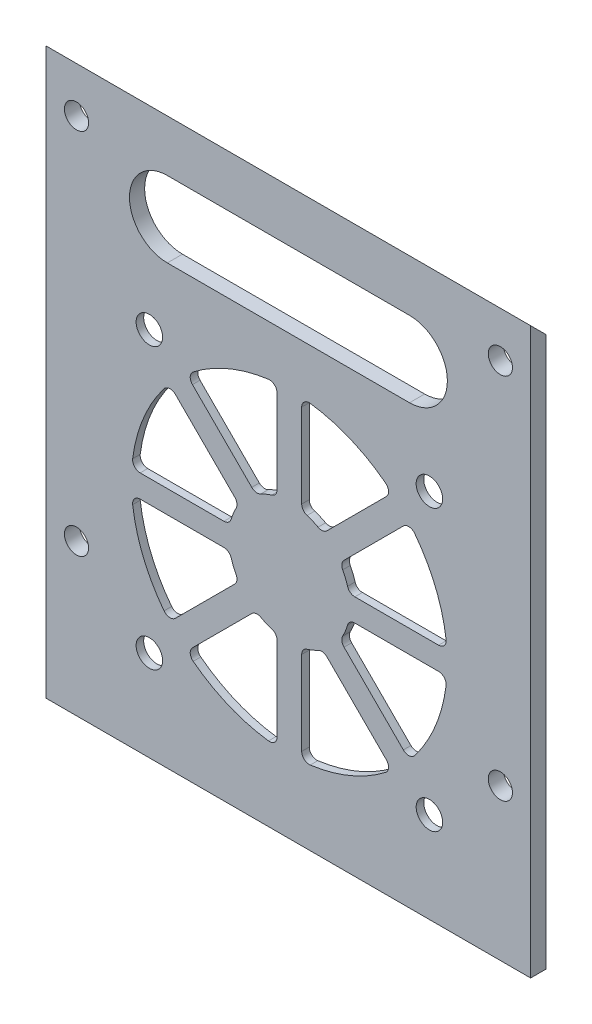
SolidWorks part; units mm, degrees
ref_plane "Płaszczyzna przednia" through (0, 0, 0) normal (0, 0, 1) x (1, 0, 0)
ref_plane "Płaszczyzna górna" through (0, 0, 0) normal (0, 1, 0) x (1, 0, 0)
ref_plane "Płaszczyzna prawa" through (0, 0, 0) normal (1, 0, 0) x (0, 0, -1)
sketch "Szkic1" plane through (0, 0, 0) normal (0, 0, 1) x (1, 0, 0)
  line L1 (-64, 0) -> (0, 0)
  line L2 (-64, 0) -> (-64, 72.64)
  line L3 (-64, 72.64) -> (0, 72.64)
  line L4 (0, 0) -> (0, 72.64)
  line L5 (0, 72.64) -> (-64, 72.64)
  line L6 (0, 72.64) -> (0, 74.64)
  line L7 (0, 74.64) -> (-64, 74.64)
  line L8 (-64, 72.64) -> (-64, 74.64)
extrude "Dodanie-wyciągnięcie1" add sketch "Szkic1" along normal blind 2 contours L8 L3 L6 L7 | L1 L4 L3 L2 region at (-32, 36.32, 0) region at (-32, 73.64, 0)
chamfer "Sfazowanie1" distance 2 angle 45 1 edges at (-32, 74.64, 0)
sketch "Szkic2" plane through (0, 0, 2) normal (0, 0, 1) x (1, 0, 0)
  line L0 (-56, 16) -> (-64, 16) construction
  line L2 (0, 72.64) -> (-64, 72.64) construction
  line L3 (0, 0) -> (0, 74.64) construction
  line L4 (-64, 0) -> (-64, 74.64) construction
  line L5 (-8, 16) -> (0, 16) construction
  line L6 (-56, 0) -> (-56, 16) construction
  line L7 (-64, 0) -> (0, 0) construction
  line L8 (-8, 0) -> (-8, 16) construction
  line L9 (-8, 16) -> (-8, 24) construction
  line L10 (-56, 16) -> (-56, 24) construction
  line L11 (-56, 72.64) -> (-56, 64.64) construction
  line L12 (-8, 72.64) -> (-8, 64.64) construction
  line L13 (-56, 64.64) -> (-64, 64.64) construction
  line L14 (-8, 64.64) -> (0, 64.64) construction
  line L15 (-56, 64.64) -> (-64, 72.64) construction
  line L16 (-8, 72.64) -> (0, 64.64) construction
  line L17 (-56, 24) -> (-64, 16) construction
  line L18 (-8, 24) -> (0, 16) construction
  circle A0 centre (-60, 20) radius 1.6
  circle A1 centre (-4, 20) radius 1.6
  circle A2 centre (-4, 68.64) radius 1.6
  circle A3 centre (-60, 68.64) radius 1.6
extrude "Wytnij-wyciągnięcie1" cut sketch "Szkic2" against normal blind 2
sketch "Szkic3" plane through (0, 0, 0) normal (0, 0, -1) x (-1, 0, 0)
  line L0 (31.8747, 30.5) -> (52.7469, 30.5)
  line L1 (31.8747, 30.5) -> (31.8747, 51.3722)
  line L2 (31.8747, 30.5) -> (11.0024, 30.5)
  line L3 (31.8747, 30.5) -> (31.8747, 9.6278)
  line L4 (31.8747, 30.5) -> (46.6336, 45.2589)
  line L5 (31.8747, 30.5) -> (17.1158, 45.2589)
  line L6 (31.8747, 30.5) -> (17.1158, 15.7411)
  line L7 (31.8747, 30.5) -> (46.6336, 15.7411)
  line L8 (17.1158, 45.2589) -> (46.6336, 15.7411) construction
  line L9 (18.2403, 46.3834) -> (47.7581, 16.8656)
  line L10 (15.9912, 44.1344) -> (45.509, 14.6166)
  line L11 (31.8747, 51.3722) -> (31.8747, 9.6278) construction
  line L12 (33.5024, 51.3722) -> (33.5024, 9.6278)
  line L13 (30.2469, 51.3722) -> (30.2469, 9.6278)
  line L14 (46.6336, 45.2589) -> (17.1158, 15.7411) construction
  line L15 (47.7581, 44.1344) -> (18.2403, 14.6166)
  line L16 (45.509, 46.3834) -> (15.9912, 16.8656)
  line L17 (52.7469, 30.5) -> (11.0024, 30.5) construction
  line L18 (52.7469, 29) -> (11.0024, 29)
  line L19 (52.7469, 32) -> (11.0024, 32)
  circle A0 centre (31.8747, 30.5) radius 20.8722
  circle A1 centre (31.8747, 30.5) radius 8
  arc A2 (18.2403, 46.3834) -> (15.9912, 44.1344) centre (17.1158, 45.2589) ccw
  arc A3 (45.509, 14.6166) -> (47.7581, 16.8656) centre (46.6336, 15.7411) ccw
  arc A4 (33.5024, 51.3722) -> (30.2469, 51.3722) centre (31.8747, 51.3722) ccw
  arc A5 (30.2469, 9.6278) -> (33.5024, 9.6278) centre (31.8747, 9.6278) ccw
  arc A6 (47.7581, 44.1344) -> (45.509, 46.3834) centre (46.6336, 45.2589) ccw
  arc A7 (15.9912, 16.8656) -> (18.2403, 14.6166) centre (17.1158, 15.7411) ccw
  arc A8 (52.7469, 29) -> (52.7469, 32) centre (52.7469, 30.5) ccw
  arc A9 (11.0024, 32) -> (11.0024, 29) centre (11.0024, 30.5) ccw
  point P4 (31.8747, 30.5)
  point P17 (31.8747, 30.5)
  point P22 (31.8747, 30.5)
  point P27 (31.8747, 30.5)
extrude "Wytnij-wyciągnięcie2" cut sketch "Szkic3" against normal blind 10 contours A1 L10 A0 L19 | A1 L18 A0 L16 | A1 L13 A0 L9 | A1 L16 A0 L12 | A1 L19 A0 L15 | A1 L9 A0 L18 | A1 L12 A0 L10 | A1 L15 A0 L13 region at (-46.2358, 36.4001, 0) region at (-46.2358, 24.5999, 0) region at (-37.8435, 44.8616, 0) region at (-37.8435, 16.1384, 0) region at (-25.9058, 44.8616, 0) region at (-17.5136, 36.4001, 0) region at (-17.5136, 24.5999, 0) region at (-25.9058, 16.1384, 0)
fillet "Zaokrąglenie1" radius 1 32 edges at (-39.7328, 32, 1) (-52.6929, 32, 1) (-38.5432, 34.9194, 1) (-47.7152, 44.0915, 1) (-33.5024, 51.3087, 1) (-45.4661, 46.3405, 1) (-36.2941, 37.1685, 1) (-33.5024, 38.3326, 1) (-18.2832, 46.3405, 1) (-30.2469, 51.3087, 1) (-30.2469, 38.3326, 1) (-27.4553, 37.1685, 1) (-16.0341, 44.0915, 1) (-25.2062, 34.9194, 1) (-24.0166, 32, 1) (-11.0564, 32, 1) (-16.0341, 16.9085, 1) (-25.2062, 26.0806, 1) (-24.0166, 29, 1) (-11.0564, 29, 1) (-18.2832, 14.6595, 1) (-27.4553, 23.8315, 1) (-30.2469, 22.6674, 1) (-30.2469, 9.6913, 1) (-33.5024, 9.6913, 1) (-45.4661, 14.6595, 1) (-33.5024, 22.6674, 1) (-36.2941, 23.8315, 1) (-47.7152, 16.9085, 1) (-52.6929, 29, 1) (-39.7328, 29, 1) (-38.5432, 26.0806, 1)
sketch "Szkic4" plane through (0, 0, 0) normal (0, 0, -1) x (-1, 0, 0)
  circle A0 centre (13.3747, 49) radius 1.75
  circle A1 centre (50.3747, 49) radius 1.75
  circle A2 centre (50.3747, 12) radius 1.75
  circle A3 centre (13.3747, 12) radius 1.75
extrude "Wytnij-wyciągnięcie3" cut sketch "Szkic4" against normal blind 10
sketch "Szkic5" plane through (0, 0, 0) normal (0, 0, -1) x (-1, 0, 0)
  line L0 (32, 53) -> (64, 53) construction
  line L1 (51.3747, 53) -> (12.3747, 53) construction
  line L2 (64, 0) -> (64, 72.64) construction
  line L3 (32, 53) -> (0.0018, 53) construction
  line L5 (32, 72.64) -> (64, 53) construction
  line L6 (64, 72.64) -> (0, 72.64) construction
  line L7 (32, 72.64) -> (0.0018, 53) construction
  line L8 (16.0009, 62.82) -> (16.0009, 53) construction
  line L9 (48, 62.82) -> (48, 53) construction
  line L10 (16.0009, 62.82) -> (48, 62.82) construction
  line L11 (16.0009, 67.82) -> (48, 67.82)
  line L12 (16.0009, 57.82) -> (48, 57.82)
  arc A0 (16.0009, 67.82) -> (16.0009, 57.82) centre (16.0009, 62.82) ccw
  arc A1 (48, 57.82) -> (48, 67.82) centre (48, 62.82) ccw
  point P16 (32.0005, 62.82)
extrude "Wytnij-wyciągnięcie4" cut sketch "Szkic5" against normal blind 10
sketch "Szkic6" plane through (0, 0, 0) normal (0, 0, -1) x (-1, 0, 0)
  line L0 (8, 55) -> (56, 55)
  line L1 (56, 8) -> (8, 8)
  line L2 (8, 8) -> (8, 55)
  line L3 (56, 8) -> (56, 55)
extrude "Wytnij-wyciągnięcie5" cut sketch "Szkic6" against normal blind 1
